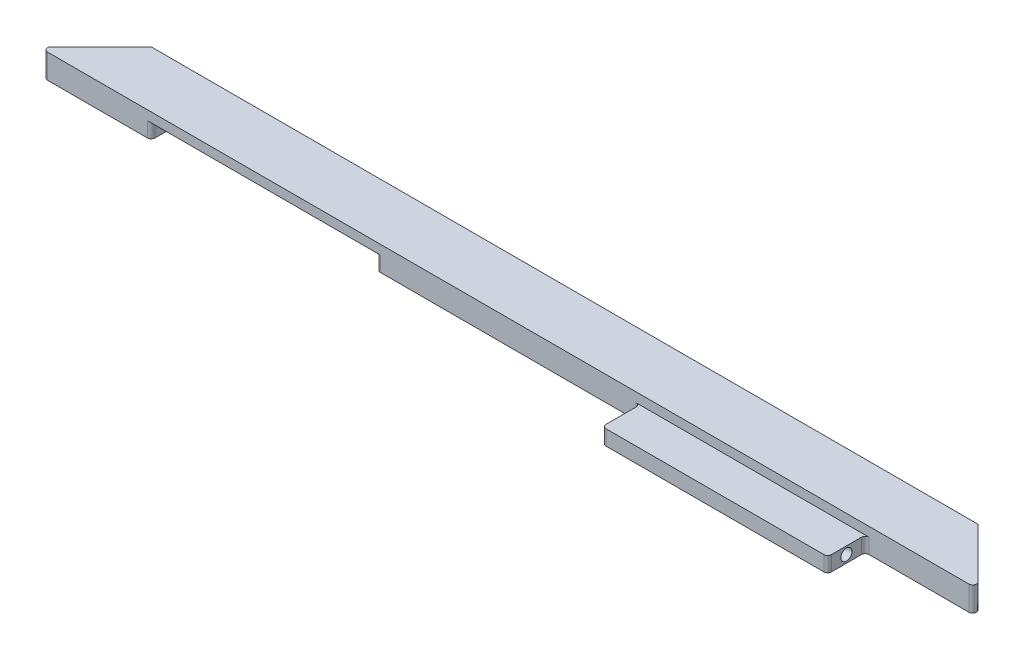
SolidWorks part; units mm, degrees
material "99.5% Aluminum Oxide"
ref_plane "Front Plane" through (0, 0, 0) normal (0, 0, 1) x (1, 0, 0)
ref_plane "Top Plane" through (0, 0, 0) normal (0, 1, 0) x (1, 0, 0)
ref_plane "Right Plane" through (0, 0, 0) normal (1, 0, 0) x (0, 0, -1)
sketch "Sketch1" plane through (0, 0, 0) normal (0, 1, 0) x (1, 0, 0)
  line L1 (-125, -10) -> (125, -10)
  line L2 (-125, -10) -> (-125, 10) construction
  line L3 (-105, 10) -> (105, 10)
  line L4 (125, -10) -> (125, 10) construction
  line L5 (-125, -10) -> (125, 10) construction
  line L6 (-125, 10) -> (125, -10) construction
  line L8 (-125, -10) -> (-105, 10)
  line L9 (125, -10) -> (105, 10)
  line L10 (-125, 10) -> (-105, 10) construction
  line L11 (105, 10) -> (125, 10) construction
  point P0 (0, 0)
  dimension "D1" = 250
  dimension "D2" = 20
  dimension "D3" = 45
  dimension "D4" = 45
extrude "Boss-Extrude1" add sketch "Sketch1" along normal mid plane 6.5
sketch "Sketch3" plane through (0, -3.25, 0) normal (0, -1, 0) x (1, 0, 0)
  line L0 (-125, 10) -> (125, 10) construction
  line L1 (35, 10) -> (95, 10)
  line L2 (35, 10) -> (35, 20)
  line L3 (35, 20) -> (95, 20)
  line L4 (95, 10) -> (95, 20)
  point P6 (125, 10)
  dimension "D1" = 30
  dimension "D2" = 60
  dimension "D3" = 10
extrude "Boss-Extrude3" add sketch "Sketch3" against normal blind 4
sketch "Sketch4" plane through (0, -3.25, 0) normal (0, -1, 0) x (1, 0, 0)
  line L0 (-125, 10) -> (35, 10) construction
  line L1 (-95, 10) -> (-35, 10)
  line L2 (-95, 10) -> (-95, 0)
  line L3 (-95, 0) -> (-35, 0)
  line L4 (-35, 10) -> (-35, 0)
  line L5 (35, 20) -> (35, 10) construction
  line L6 (95, 20) -> (35, 20) construction
  point P11 (-125, 10)
  dimension "D1" = 30
extrude "Cut-Extrude1" cut sketch "Sketch4" against normal blind 4
sketch "Sketch5" plane through (-35, 0, 0) normal (-1, 0, 0) x (0, 0, 1)
  line L0 (5, 0.75) -> (5, -3.25) construction
  line L1 (0, 0.75) -> (10, 0.75) construction
  line L2 (0, -3.25) -> (10, -3.25) construction
  line L3 (5, -0.25) -> (5, -2.25)
  arc A0 (5, -0.25) -> (5, -2.25) centre (5, -1.25) ccw
  dimension "D1" = 1
revolve "Cut-Revolve1" cut sketch "Sketch5" angle 360 about L0
sketch "Sketch6" plane through (-95, 0, 0) normal (1, 0, 0) x (0, 0, -1)
  line L0 (-5, 0.75) -> (-5, -3.25) construction
  line L1 (-10, 0.75) -> (0, 0.75) construction
  line L2 (-10, -3.25) -> (0, -3.25) construction
  line L3 (-5, -0.25) -> (-5, -2.25)
  arc A0 (-5, -0.25) -> (-5, -2.25) centre (-5, -1.25) cw
  dimension "D1" = 1
revolve "Cut-Revolve2" cut sketch "Sketch6" angle 360 about L0
sketch "Sketch7" plane through (35, 0, 0) normal (-1, 0, 0) x (0, 0, 1)
  line L0 (10, -1.25) -> (20, -1.25) construction
  line L1 (10, 0.75) -> (10, -3.25) construction
  line L2 (20, 0.75) -> (20, -3.25) construction
  circle A0 centre (15, -1.25) radius 1.5
  dimension "D1" = 3
extrude "Cut-Extrude2" cut sketch "Sketch7" against normal blind 7
sketch "Sketch8" plane through (95, 0, 0) normal (1, 0, 0) x (0, 0, -1)
  line L0 (-20, -1.25) -> (-10, -1.25) construction
  line L1 (-20, 0.75) -> (-20, -3.25) construction
  line L2 (-10, 0.75) -> (-10, -3.25) construction
  circle A0 centre (-15, -1.25) radius 1.5
  dimension "D1" = 3
extrude "Cut-Extrude3" cut sketch "Sketch8" against normal blind 7
chamfer "Chamfer1" distance 5 angle 45 1 edges at (0, 3.25, -10)
sketch "Sketch9" plane through (0, -3.25, 0) normal (0, -1, 0) x (1, 0, 0)
  line L0 (-32, 7) -> (-32, -7)
  line L1 (-32, -7) -> (103.7574, -7)
  line L2 (103.7574, -7) -> (117.7574, 7)
  line L3 (117.7574, 7) -> (-32, 7)
  line L4 (125, 10) -> (105, -10) construction
  line L5 (-35, 0) -> (-35, 10) construction
  line L6 (-35, 10) -> (35, 10) construction
  line L7 (105, -10) -> (-105, -10) construction
  line L8 (-117.7574, 7) -> (-103.7574, -7)
  line L9 (-103.7574, -7) -> (-98, -7)
  line L10 (-98, -7) -> (-98, 7)
  line L11 (-98, 7) -> (-117.7574, 7)
  line L12 (-125, 10) -> (-95, 10) construction
  line L13 (-95, 10) -> (-95, 0) construction
  line L14 (-105, -10) -> (-125, 10) construction
  dimension "D1" = 3
  dimension "D2" = 3
  dimension "D3" = 3
  dimension "D4" = 3
  dimension "D5" = 3
  dimension "D6" = 3
  dimension "D7" = 3
  dimension "D8" = 3
extrude "Cut-Extrude4" cut sketch "Sketch9" against normal offset from surface (3.75 mm away) 2.75 up to face at (0, 3.25, 2.5)
fillet "Fillet3" radius 1 14 edges at (35, -1.25, 10) (95, -1.25, 10) (95, -1.25, 20) (35, -1.25, 20) (-95, -1.25, 10) (-35, -1.25, 0) (-95, -1.25, 0) (-35, -1.25, 10) (125, 0, 10) (-125, 0, 10) (-117.7574, -1.375, 7) (-103.7574, -1.375, -7) (117.7574, -1.375, 7) (103.7574, -1.375, -7)
fillet "Fillet4" radius 6 4 edges at (-32, -1.375, -7) (-32, -1.375, 7) (-98, -1.375, 7) (-98, -1.375, -7)
